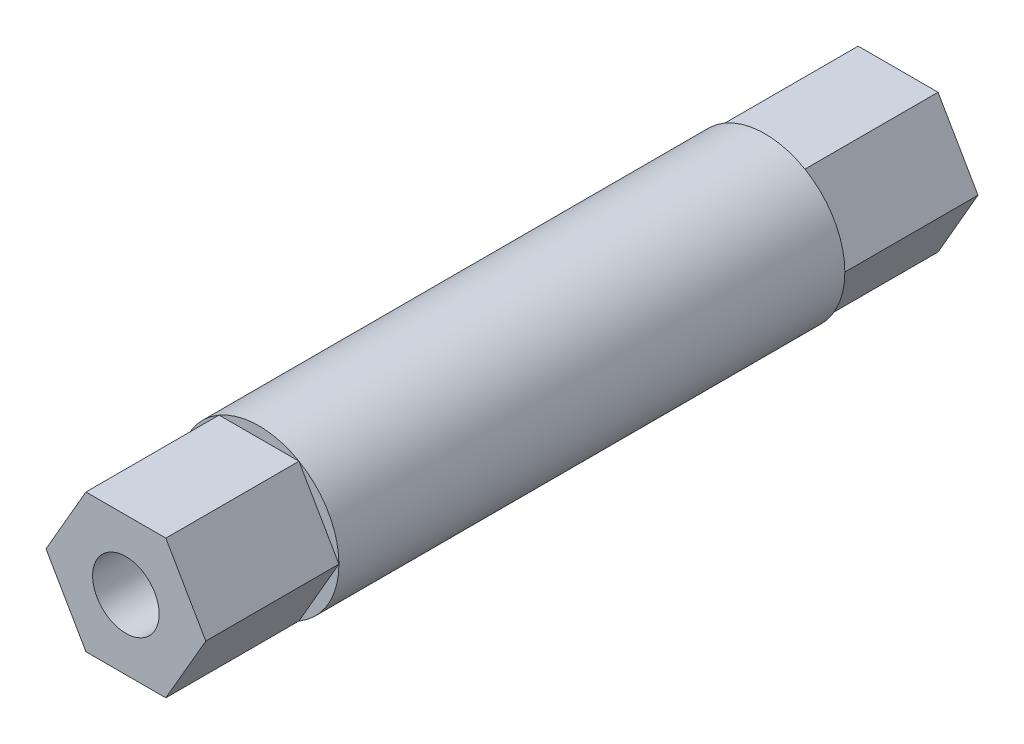
SolidWorks part; units mm, degrees
material "1060 Alloy"
ref_plane "Front Plane" through (0, 0, 0) normal (0, 0, 1) x (1, 0, 0)
ref_plane "Top Plane" through (0, 0, 0) normal (0, 1, 0) x (1, 0, 0)
ref_plane "Right Plane" through (0, 0, 0) normal (1, 0, 0) x (0, 0, -1)
sketch "Sketch1" plane through (0, 0, 0) normal (0, 0, 1) x (1, 0, 0)
  circle A0 centre (0, 0) radius 3
  dimension "D1" = 6
extrude "Boss-Extrude1" add sketch "Sketch1" along normal blind 29
ref_plane "Plane1" through (0, 0, 14.5) normal (0, 0, -1) x (-1, 0, 0)
sketch "Sketch3" plane through (0, 0, 29) normal (0, 0, 1) x (1, 0, 0)
  line L1 (3, 0) -> (1.5, 2.5981)
  line L2 (1.5, 2.5981) -> (-1.5, 2.5981)
  line L3 (-1.5, 2.5981) -> (-3, 0)
  line L4 (-3, 0) -> (-1.5, -2.5981)
  line L5 (-1.5, -2.5981) -> (1.5, -2.5981)
  line L6 (1.5, -2.5981) -> (3, 0)
  circle A0 centre (0, 0) radius 2.5981 construction
  circle M7 centre (0, 0) radius 3
extrude "Cut-Extrude1" cut sketch "Sketch3" against normal blind 5 contours L3 M7 | L1 M7 | L2 M7 | L4 M7 | L5 M7 | L6 M7 region at (2.3901, -1.3799, 29) region at (2.3901, 1.3799, 29) region at (0, 2.7598, 29) region at (0, -2.7598, 29) region at (-2.3901, 1.3799, 29) region at (-2.3901, -1.3799, 29)
mirror "Mirror1" about plane through (0, 0, 14.5) normal (0, 0, -1) of "Cut-Extrude1"
hole_wizard "Tap Drill for M3x0.5 Tap1" positions "Sketch4" profile "Sketch6" hole size "M3x0.5" standard "ANSI Metric"
sketch "Sketch4" plane through (0, 0, 29) normal (0, 0, 1) x (1, 0, 0)
  point P0 (0, 0)
sketch "Sketch6" plane through (0, 0, 29) normal (1, 0, 0) x (0, -1, 0)
  line L0 (0, 0) -> (0, 5.7511)
  line L1 (0, 5.7511) -> (1.25, 5)
  line L2 (1.25, 5) -> (1.25, 0)
  line L5 (1.25, 0) -> (0, 0)
  line L10 (0, 5.7511) -> (-1.25, 5) construction
  line L11 (0, -6.35) -> (0, 107.95) construction
  dimension "Hole Dia." = 2.5
  dimension "Hole Depth" = 5
  dimension "Drill Angle" = 118
mirror "Mirror2" about plane through (0, 0, 14.5) normal (0, 0, -1) of "Tap Drill for M3x0.5 Tap1"
